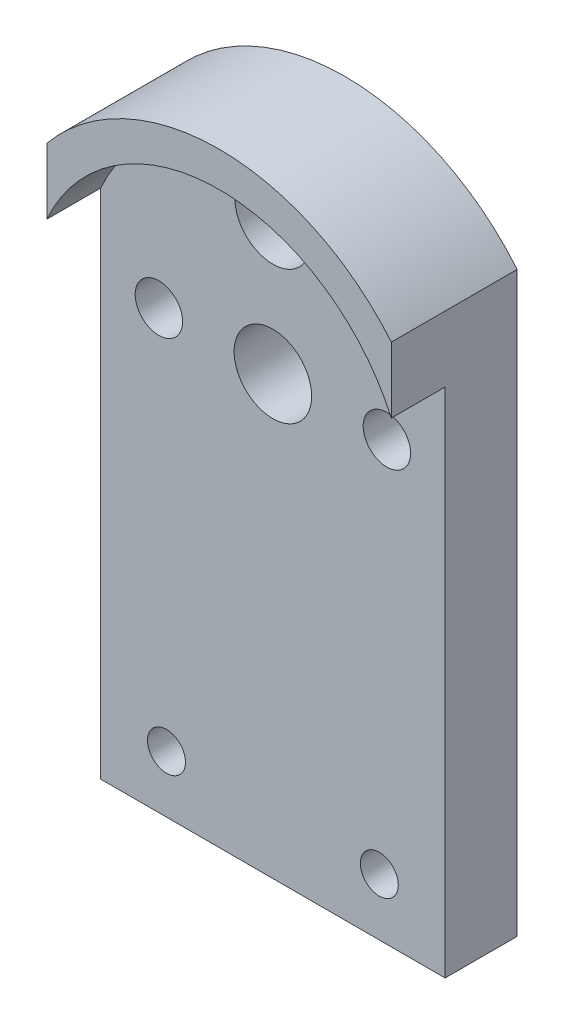
SolidWorks part; units mm, degrees
material "Onyx"
ref_plane "Front" through (0, 0, 0) normal (0, 0, 1) x (1, 0, 0)
ref_plane "Top" through (0, 0, 0) normal (0, 1, 0) x (1, 0, 0)
ref_plane "Right" through (0, 0, 0) normal (1, 0, 0) x (0, 0, -1)
sketch "Sketch2" plane through (0, 0, 0) normal (0, 0, 1) x (1, 0, 0)
  line L0 (0, 15.3416) -> (0, -36.5125) construction
  line L1 (14.3891, -36.5125) -> (-14.3891, -36.5125)
  line L2 (14.3891, -36.5125) -> (14.3891, 11.7424)
  line L4 (-14.3891, -36.5125) -> (-14.3891, 11.7424)
  line L5 (-15.4933, 0) -> (15.4933, 0) construction
  line L6 (-14.3891, 15.3416) -> (14.3891, 15.3416) construction
  line L8 (-14.3891, -28.0416) -> (14.3891, -28.0416) construction
  line L9 (-14.3891, -31.8516) -> (14.3891, -31.8516) construction
  line L10 (-8.89, 15.3416) -> (-8.89, -31.8516) construction
  line L11 (8.89, 15.3416) -> (8.89, -31.8516) construction
  circle A1 centre (0, 0) radius 3.2385
  arc A2 (-15.4933, 0) -> (15.4933, 0) centre (0, -0.1524) cw construction
  arc A7 (-14.3891, 11.7424) -> (14.3891, 11.7424) centre (0, -0.1524) cw
  arc A8 (-18.6681, 0.0312) -> (18.6681, 0.0312) centre (0, -0.1524) cw construction
  point P10 (0, 0)
  dimension "D4" = 6.477
  dimension "D2" = 15.494
  dimension "D1" = 28.7782
  dimension "D3" = 15.3416
  dimension "D8" = 5.4991
  dimension "D9" = 5.4991
  dimension "D5" = 43.3832
  dimension "D11" = 3.81
  dimension "D12" = 4.6609
  dimension "D6" = 3.175
extrude "Boss-Extrude1" add sketch "Sketch2" along normal blind 6.0198
sketch "Sketch12" plane through (0, 0, 6.0198) normal (0, 0, 1) x (1, 0, 0)
  line L2 (-14.3891, 6.2471) -> (-14.3891, 11.7424)
  line L3 (14.3891, 11.7424) -> (14.3891, 6.2471)
  arc A0 (15.4933, 0) -> (-15.4933, 0) centre (0, -0.1524) ccw construction
  arc A1 (15.4933, 0) -> (-15.4933, 0) centre (0, -0.1524) ccw construction
  arc A3 (-14.3891, 11.7424) -> (14.3891, 11.7424) centre (0, -0.1524) cw
  arc A4 (14.3891, 11.7424) -> (-14.3891, 11.7424) centre (0, -0.1524) ccw construction
  arc A5 (-14.3891, 6.2471) -> (14.3891, 6.2471) centre (0, -0.1524) cw
  dimension "D1" = 0.254
extrude "Boss-Extrude5" add sketch "Sketch12" along normal blind 4.4958
sketch "Sketch5" plane through (0, 0, 6.0198) normal (0, 0, 1) x (1, 0, 0)
  line L0 (-10.4775, 15.2993) -> (-10.4775, -36.5125) construction
  line L2 (-14.3891, -36.5125) -> (14.3891, -36.5125) construction
  line L3 (10.4775, 15.2993) -> (10.4775, -36.5125) construction
  line L4 (-10.4775, -10.6066) -> (10.4775, -10.6066) construction
  line L5 (0, 0) -> (0, -10.6066) construction
  circle A0 centre (-10.4775, -15.748) radius 1.9812 construction
  circle A1 centre (10.4775, -15.748) radius 1.9812 construction
  circle A2 centre (0, 0) radius 9.525 construction
  circle A3 centre (-9.525, 0) radius 1.9812
  circle A4 centre (9.525, 0) radius 1.9812
  arc A5 (14.3891, -12.0472) -> (-14.3891, -12.0472) centre (0, -0.1524) ccw construction
  dimension "D2" = 3.9624
  dimension "D3" = 19.05
  dimension "D1" = 20.955
  dimension "D5" = 15.748
extrude "Cut-Extrude2_EncoderScrewHoles" cut sketch "Sketch5" against normal through all
sketch "Sketch11" plane through (0, 0, 0) normal (0, 0, -1) x (-1, 0, 0)
  line L0 (14.3891, 11.7424) -> (14.3891, -36.5125) construction
  line L1 (9.525, -3.3729) -> (12.446, -1.6864)
  line L2 (12.446, -1.6864) -> (12.446, 1.6864)
  line L3 (12.446, 1.6864) -> (9.525, 3.3729)
  line L4 (9.525, 3.3729) -> (6.604, 1.6864)
  line L5 (6.604, 1.6864) -> (6.604, -1.6864)
  line L6 (6.604, -1.6864) -> (9.525, -3.3729)
  line L7 (-14.3891, -36.5125) -> (-14.3891, 11.7424) construction
  line L8 (-6.604, -1.6864) -> (-6.604, 1.6864)
  line L9 (-6.604, 1.6864) -> (-9.525, 3.3729)
  line L10 (-9.525, 3.3729) -> (-12.446, 1.6864)
  line L11 (-12.446, 1.6864) -> (-12.446, -1.6864)
  line L12 (-12.446, -1.6864) -> (-9.525, -3.3729)
  line L13 (-9.525, -3.3729) -> (-6.604, -1.6864)
  circle A0 centre (9.525, 0) radius 2.921 construction
  circle A1 centre (-9.525, 0) radius 2.921 construction
  circle A3 centre (-9.525, 0) radius 1.9812 construction
  dimension "D1" = 5.842
extrude "Cut-Extrude4" cut sketch "Sketch11" against normal blind 2.8448
sketch "Sketch13" plane through (0, 0, 6.0198) normal (0, 0, 1) x (1, 0, 0)
  line L0 (0, 0) -> (0, -36.5125) construction
  line L1 (-14.3891, -36.5125) -> (14.3891, -36.5125) construction
  line L2 (8.89, -31.75) -> (-8.89, -31.75) construction
  circle A1 centre (8.89, -31.75) radius 1.5875
  circle A2 centre (-8.89, -31.75) radius 1.5875
  point P9 (0, -31.75)
  dimension "D1" = 3.175
  dimension "D3" = 8.89
  dimension "D2" = 4.7625
extrude "Cut-Extrude5" cut sketch "Sketch13" against normal through all
ref_axis "Axis1" through (0, 0, 36.0066) along (0, 0, -1)
sketch "Sketch7" plane through (0, 0, 0) normal (0, 0, -1) x (-1, 0, 0)
  line L0 (0, 18.5166) -> (0, -36.5125) construction
  line L2 (14.3891, -36.5125) -> (-14.3891, -36.5125) construction
  line L3 (-14.3891, -15.875) -> (14.3891, -15.875) construction
  line L4 (14.3891, 6.2471) -> (14.3891, -36.5125) construction
  circle A0 centre (0, -15.875) radius 3.9688
  arc A1 (14.3891, -12.0472) -> (-14.3891, -12.0472) centre (0, -0.1524) ccw construction
  dimension "D1" = 7.9375
  dimension "D2" = 15.875
extrude "Boss-Extrude4" add sketch "Sketch7" along normal blind 3.175
sketch "Sketch14" plane through (0, 0, 0) normal (0, 0, -1) x (-1, 0, 0)
  line L0 (0, 0) -> (0, 18.5166) construction
  arc A0 (14.3891, 11.7424) -> (-14.3891, 11.7424) centre (0, -0.1524) ccw construction
  circle A1 centre (0, 11.1125) radius 3.175
  dimension "D1" = 6.35
  dimension "D2" = 11.1125
extrude "Cut-Extrude6" cut sketch "Sketch14" against normal through all
equation "\"D1@Boss-Extrude5\"=0.354/2"
equation "\"D2@Sketch7\"=1.25/2"
equation "\"D11@Sketch2\"=0.15000000"
equation "\"D12@Sketch2\"=0.1210000+0.0625"
